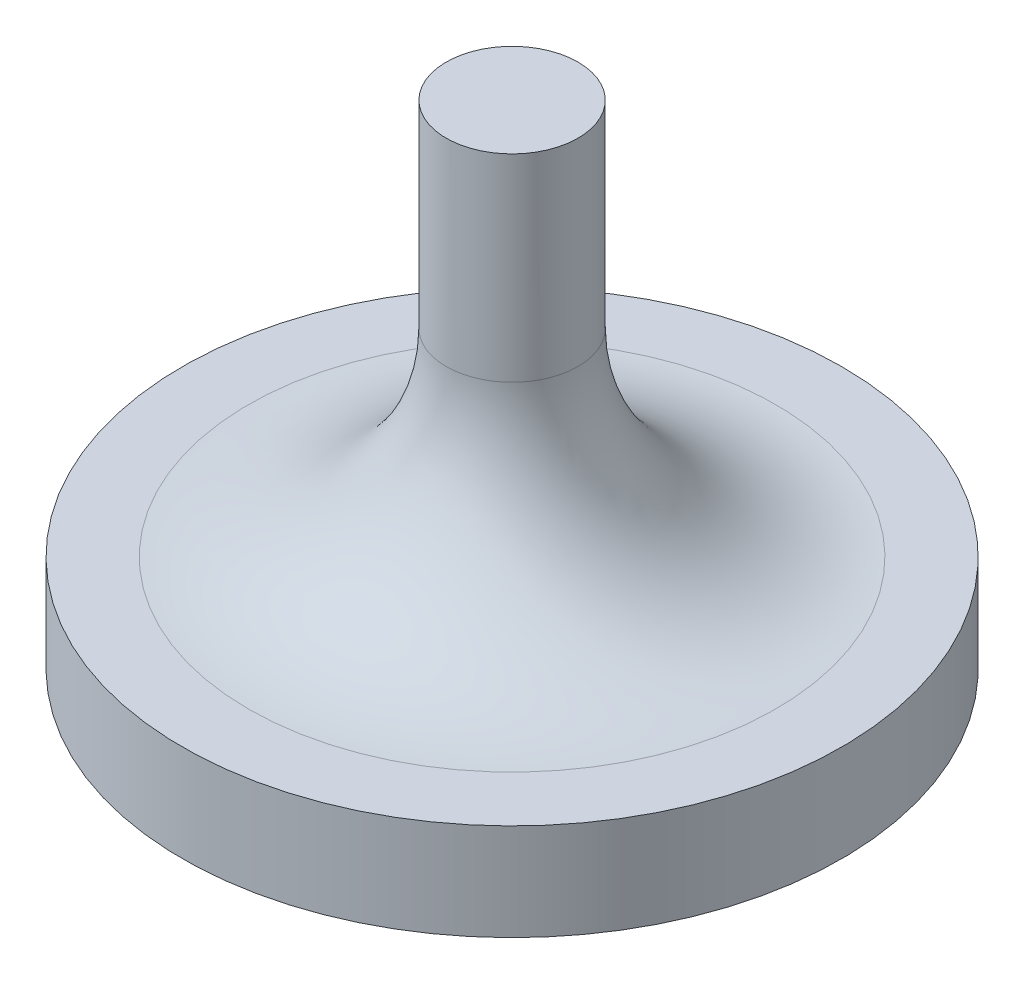
SolidWorks part; units mm, degrees
material "PS HI"
ref_plane "Front Plane" through (0, 0, 0) normal (0, 0, 1) x (1, 0, 0)
ref_plane "Top Plane" through (0, 0, 0) normal (0, 1, 0) x (1, 0, 0)
ref_plane "Right Plane" through (0, 0, 0) normal (1, 0, 0) x (0, 0, -1)
sketch "Sketch2" plane through (0, 0, 0) normal (1, 0, 0) x (0, 0, -1)
  line L0 (0, 0) -> (0, 50)
  line L1 (0, 55) -> (0, -55) construction
  line L2 (0, 50) -> (5, 50)
  line L3 (5, 50) -> (5, 20)
  line L4 (5, 20) -> (25, 20)
  line L5 (25, 20) -> (25, 12.6603)
  line L6 (25, 12.6603) -> (5, 12.6603)
  line L7 (5, 12.6603) -> (5, 8.6603)
  line L8 (5, 8.6603) -> (0, 0)
  dimension "D1" = 5
  dimension "D2" = 25
  dimension "D3" = 30
  dimension "D4" = 7.3397
  dimension "D5" = 50
  dimension "D6" = 30
revolve "Revolve1" add sketch "Sketch2" angle 360 about L0
fillet "Fillet1" radius 50 1 edges at (0, 12.6603, -5)
fillet "Fillet2" radius 15 1 edges at (0, 20, -5)
